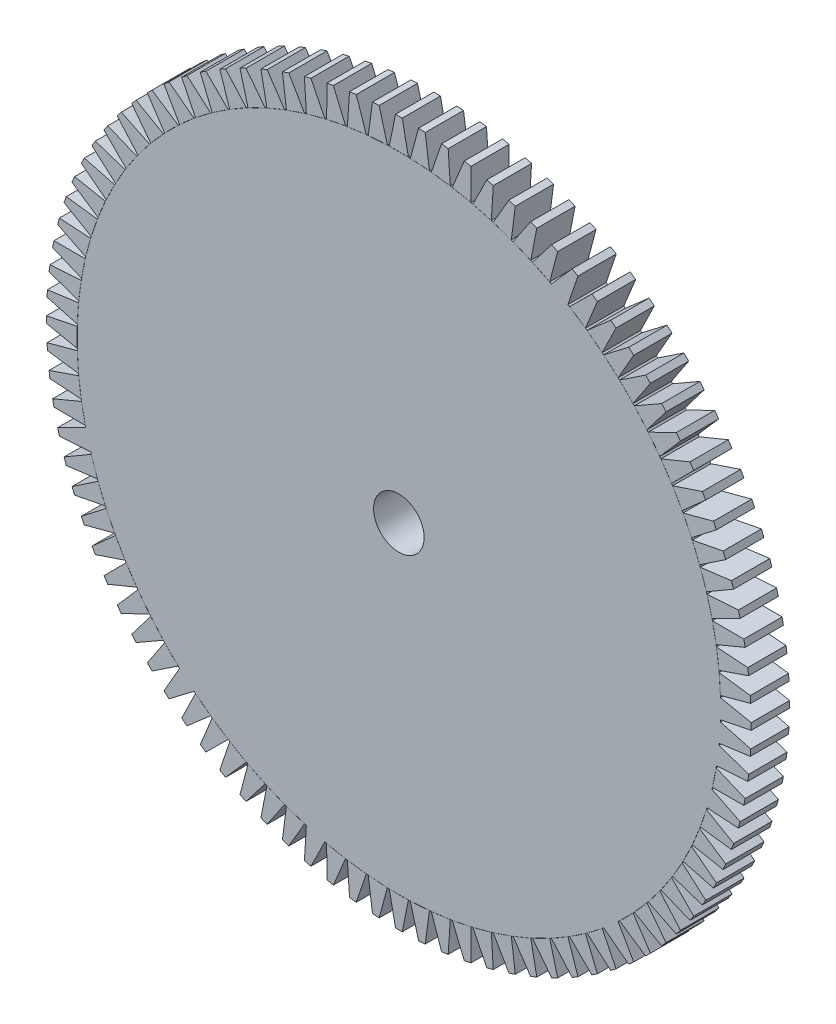
SolidWorks part; units mm, degrees
material "ABS"
ref_plane "Front Plane" through (0, 0, 0) normal (0, 0, 1) x (1, 0, 0)
ref_plane "Top Plane" through (0, 0, 0) normal (0, 1, 0) x (1, 0, 0)
ref_plane "Right Plane" through (0, 0, 0) normal (1, 0, 0) x (0, 0, -1)
sketch "Sketch1" plane through (0, 0, 0) normal (0, 0, 1) x (1, 0, 0)
  line L0 (-0.381, 12.7959) -> (0.381, 12.7959)
  line L1 (0, -15.4229) -> (0, 15.4229) construction
  line L2 (-0.1333, 14.0214) -> (0.1333, 14.0202)
  line L3 (-0.1333, 14.0214) -> (-0.381, 12.7959)
  line L4 (0.1333, 14.0202) -> (0.381, 12.7959)
  line L5 (1.05, 13.9814) -> (1.2171, 12.7436)
  line L6 (0.4567, 12.7935) -> (1.2171, 12.7436)
  line L7 (0.784, 14.0001) -> (0.4567, 12.7935)
  line L8 (0.784, 14.0001) -> (1.05, 13.9814)
  line L9 (1.9622, 13.8828) -> (2.0479, 12.6367)
  line L10 (1.2925, 12.7362) -> (2.0479, 12.6367)
  line L11 (1.698, 13.9189) -> (1.2925, 12.7362)
  line L12 (1.698, 13.9189) -> (1.9622, 13.8828)
  line L13 (2.866, 13.7248) -> (2.87, 12.4757)
  line L14 (2.1227, 12.6244) -> (2.87, 12.4757)
  line L15 (2.6047, 13.778) -> (2.1227, 12.6244)
  line L16 (2.6047, 13.778) -> (2.866, 13.7248)
  line L17 (3.7575, 13.5079) -> (3.6798, 12.2613)
  line L18 (2.9438, 12.4585) -> (3.6798, 12.2613)
  line L19 (3.5002, 13.5782) -> (2.9438, 12.4585)
  line L20 (3.5002, 13.5782) -> (3.7575, 13.5079)
  line L21 (4.6329, 13.2333) -> (4.4739, 11.9944)
  line L22 (3.7523, 12.2393) -> (4.4739, 11.9944)
  line L23 (4.3808, 13.3202) -> (3.7523, 12.2393)
  line L24 (4.3808, 13.3202) -> (4.6329, 13.2333)
  line L25 (5.4885, 12.9019) -> (5.2488, 11.6761)
  line L26 (4.5448, 11.9677) -> (5.2488, 11.6761)
  line L27 (5.2426, 13.0051) -> (4.5448, 11.9677)
  line L28 (5.2426, 13.0051) -> (5.4885, 12.9019)
  line L29 (6.3206, 12.5153) -> (6.0012, 11.3078)
  line L30 (5.3178, 11.6448) -> (6.0012, 11.3078)
  line L31 (6.0819, 12.6344) -> (5.3178, 11.6448)
  line L32 (6.0819, 12.6344) -> (6.3206, 12.5153)
  line L33 (7.1256, 12.0751) -> (6.7279, 10.8911)
  line L34 (6.068, 11.2721) -> (6.7279, 10.8911)
  line L35 (6.8952, 12.2096) -> (6.068, 11.2721)
  line L36 (6.8952, 12.2096) -> (7.1256, 12.0751)
  line L37 (7.9001, 11.5833) -> (7.4258, 10.4278)
  line L38 (6.7922, 10.8511) -> (7.4258, 10.4278)
  line L39 (7.679, 11.7325) -> (6.7922, 10.8511)
  line L40 (7.679, 11.7325) -> (7.9001, 11.5833)
  line L41 (8.6407, 11.0418) -> (8.0919, 9.9198)
  line L42 (7.4874, 10.3836) -> (8.0919, 9.9198)
  line L43 (8.4299, 11.2051) -> (7.4874, 10.3836)
  line L44 (8.4299, 11.2051) -> (8.6407, 11.0418)
  line L45 (9.3444, 10.453) -> (8.7234, 9.3693)
  line L46 (8.1505, 9.8717) -> (8.7234, 9.3693)
  line L47 (9.1447, 10.6298) -> (8.1505, 9.8717)
  line L48 (9.1447, 10.6298) -> (9.3444, 10.453)
  line L49 (10.008, 9.8195) -> (9.3175, 8.7787)
  line L50 (8.7787, 9.3175) -> (9.3175, 8.7787)
  line L51 (9.8204, 10.0089) -> (8.7787, 9.3175)
  line L52 (9.8204, 10.0089) -> (10.008, 9.8195)
  line L53 (10.6288, 9.1439) -> (9.8717, 8.1505)
  line L54 (9.3693, 8.7234) -> (9.8717, 8.1505)
  line L55 (10.4539, 9.3452) -> (9.3693, 8.7234)
  line L56 (10.4539, 9.3452) -> (10.6288, 9.1439)
  line L57 (11.2041, 8.4291) -> (10.3836, 7.4874)
  line L58 (9.9198, 8.0919) -> (10.3836, 7.4874)
  line L59 (11.0428, 8.6415) -> (9.9198, 8.0919)
  line L60 (11.0428, 8.6415) -> (11.2041, 8.4291)
  line L61 (11.7314, 7.6783) -> (10.8511, 6.7922)
  line L62 (10.4278, 7.4258) -> (10.8511, 6.7922)
  line L63 (11.5843, 7.9008) -> (10.4278, 7.4258)
  line L64 (11.5843, 7.9008) -> (11.7314, 7.6783)
  line L65 (12.2085, 6.8946) -> (11.2721, 6.068)
  line L66 (10.8911, 6.7279) -> (11.2721, 6.068)
  line L67 (12.0762, 7.1262) -> (10.8911, 6.7279)
  line L68 (12.0762, 7.1262) -> (12.2085, 6.8946)
  line L69 (12.6333, 6.0814) -> (11.6448, 5.3178)
  line L70 (11.3078, 6.0012) -> (11.6448, 5.3178)
  line L71 (12.5165, 6.3211) -> (11.3078, 6.0012)
  line L72 (12.5165, 6.3211) -> (12.6333, 6.0814)
  line L73 (13.004, 5.2421) -> (11.9677, 4.5448)
  line L74 (11.6761, 5.2488) -> (11.9677, 4.5448)
  line L75 (12.9031, 5.489) -> (11.6761, 5.2488)
  line L76 (12.9031, 5.489) -> (13.004, 5.2421)
  line L77 (13.319, 4.3804) -> (12.2393, 3.7523)
  line L78 (11.9944, 4.4739) -> (12.2393, 3.7523)
  line L79 (13.2345, 4.6333) -> (11.9944, 4.4739)
  line L80 (13.2345, 4.6333) -> (13.319, 4.3804)
  line L81 (13.577, 3.4999) -> (12.4585, 2.9438)
  line L82 (12.2613, 3.6798) -> (12.4585, 2.9438)
  line L83 (13.5092, 3.7578) -> (12.2613, 3.6798)
  line L84 (13.5092, 3.7578) -> (13.577, 3.4999)
  line L85 (13.7768, 2.6044) -> (12.6244, 2.1227)
  line L86 (12.4757, 2.87) -> (12.6244, 2.1227)
  line L87 (13.726, 2.8662) -> (12.4757, 2.87)
  line L88 (13.726, 2.8662) -> (13.7768, 2.6044)
  line L89 (13.9176, 1.6978) -> (12.7362, 1.2925)
  line L90 (12.6367, 2.0479) -> (12.7362, 1.2925)
  line L91 (13.8841, 1.9624) -> (12.6367, 2.0479)
  line L92 (13.8841, 1.9624) -> (13.9176, 1.6978)
  line L93 (13.9989, 0.7839) -> (12.7935, 0.4567)
  line L94 (12.7436, 1.2171) -> (12.7935, 0.4567)
  line L95 (13.9827, 1.0501) -> (12.7436, 1.2171)
  line L96 (13.9827, 1.0501) -> (13.9989, 0.7839)
  line L97 (14.0202, -0.1333) -> (12.7959, -0.381)
  line L98 (12.7959, 0.381) -> (12.7959, -0.381)
  line L99 (14.0214, 0.1333) -> (12.7959, 0.381)
  line L100 (14.0214, 0.1333) -> (14.0202, -0.1333)
  line L101 (13.9814, -1.05) -> (12.7436, -1.2171)
  line L102 (12.7935, -0.4567) -> (12.7436, -1.2171)
  line L103 (14.0001, -0.784) -> (12.7935, -0.4567)
  line L104 (14.0001, -0.784) -> (13.9814, -1.05)
  line L105 (13.8828, -1.9622) -> (12.6367, -2.0479)
  line L106 (12.7362, -1.2925) -> (12.6367, -2.0479)
  line L107 (13.9189, -1.698) -> (12.7362, -1.2925)
  line L108 (13.9189, -1.698) -> (13.8828, -1.9622)
  line L109 (13.7248, -2.866) -> (12.4757, -2.87)
  line L110 (12.6244, -2.1227) -> (12.4757, -2.87)
  line L111 (13.778, -2.6047) -> (12.6244, -2.1227)
  line L112 (13.778, -2.6047) -> (13.7248, -2.866)
  line L113 (13.5079, -3.7575) -> (12.2613, -3.6798)
  line L114 (12.4585, -2.9438) -> (12.2613, -3.6798)
  line L115 (13.5782, -3.5002) -> (12.4585, -2.9438)
  line L116 (13.5782, -3.5002) -> (13.5079, -3.7575)
  line L117 (13.2333, -4.6329) -> (11.9944, -4.4739)
  line L118 (12.2393, -3.7523) -> (11.9944, -4.4739)
  line L119 (13.3202, -4.3808) -> (12.2393, -3.7523)
  line L120 (13.3202, -4.3808) -> (13.2333, -4.6329)
  line L121 (12.9019, -5.4885) -> (11.6761, -5.2488)
  line L122 (11.9677, -4.5448) -> (11.6761, -5.2488)
  line L123 (13.0051, -5.2426) -> (11.9677, -4.5448)
  line L124 (13.0051, -5.2426) -> (12.9019, -5.4885)
  line L125 (12.5153, -6.3206) -> (11.3078, -6.0012)
  line L126 (11.6448, -5.3178) -> (11.3078, -6.0012)
  line L127 (12.6344, -6.0819) -> (11.6448, -5.3178)
  line L128 (12.6344, -6.0819) -> (12.5153, -6.3206)
  line L129 (12.0751, -7.1256) -> (10.8911, -6.7279)
  line L130 (11.2721, -6.068) -> (10.8911, -6.7279)
  line L131 (12.2096, -6.8952) -> (11.2721, -6.068)
  line L132 (12.2096, -6.8952) -> (12.0751, -7.1256)
  line L133 (11.5833, -7.9001) -> (10.4278, -7.4258)
  line L134 (10.8511, -6.7922) -> (10.4278, -7.4258)
  line L135 (11.7325, -7.679) -> (10.8511, -6.7922)
  line L136 (11.7325, -7.679) -> (11.5833, -7.9001)
  line L137 (11.0418, -8.6407) -> (9.9198, -8.0919)
  line L138 (10.3836, -7.4874) -> (9.9198, -8.0919)
  line L139 (11.2051, -8.4299) -> (10.3836, -7.4874)
  line L140 (11.2051, -8.4299) -> (11.0418, -8.6407)
  line L141 (10.453, -9.3444) -> (9.3693, -8.7234)
  line L142 (9.8717, -8.1505) -> (9.3693, -8.7234)
  line L143 (10.6298, -9.1447) -> (9.8717, -8.1505)
  line L144 (10.6298, -9.1447) -> (10.453, -9.3444)
  line L145 (9.8195, -10.008) -> (8.7787, -9.3175)
  line L146 (9.3175, -8.7787) -> (8.7787, -9.3175)
  line L147 (10.0089, -9.8204) -> (9.3175, -8.7787)
  line L148 (10.0089, -9.8204) -> (9.8195, -10.008)
  line L149 (9.1439, -10.6288) -> (8.1505, -9.8717)
  line L150 (8.7234, -9.3693) -> (8.1505, -9.8717)
  line L151 (9.3452, -10.4539) -> (8.7234, -9.3693)
  line L152 (9.3452, -10.4539) -> (9.1439, -10.6288)
  line L153 (8.4291, -11.2041) -> (7.4874, -10.3836)
  line L154 (8.0919, -9.9198) -> (7.4874, -10.3836)
  line L155 (8.6415, -11.0428) -> (8.0919, -9.9198)
  line L156 (8.6415, -11.0428) -> (8.4291, -11.2041)
  line L157 (7.6783, -11.7314) -> (6.7922, -10.8511)
  line L158 (7.4258, -10.4278) -> (6.7922, -10.8511)
  line L159 (7.9008, -11.5843) -> (7.4258, -10.4278)
  line L160 (7.9008, -11.5843) -> (7.6783, -11.7314)
  line L161 (6.8946, -12.2085) -> (6.068, -11.2721)
  line L162 (6.7279, -10.8911) -> (6.068, -11.2721)
  line L163 (7.1262, -12.0762) -> (6.7279, -10.8911)
  line L164 (7.1262, -12.0762) -> (6.8946, -12.2085)
  line L165 (6.0814, -12.6333) -> (5.3178, -11.6448)
  line L166 (6.0012, -11.3078) -> (5.3178, -11.6448)
  line L167 (6.3211, -12.5165) -> (6.0012, -11.3078)
  line L168 (6.3211, -12.5165) -> (6.0814, -12.6333)
  line L169 (5.2421, -13.004) -> (4.5448, -11.9677)
  line L170 (5.2488, -11.6761) -> (4.5448, -11.9677)
  line L171 (5.489, -12.9031) -> (5.2488, -11.6761)
  line L172 (5.489, -12.9031) -> (5.2421, -13.004)
  line L173 (4.3804, -13.319) -> (3.7523, -12.2393)
  line L174 (4.4739, -11.9944) -> (3.7523, -12.2393)
  line L175 (4.6333, -13.2345) -> (4.4739, -11.9944)
  line L176 (4.6333, -13.2345) -> (4.3804, -13.319)
  line L177 (3.4999, -13.577) -> (2.9438, -12.4585)
  line L178 (3.6798, -12.2613) -> (2.9438, -12.4585)
  line L179 (3.7578, -13.5092) -> (3.6798, -12.2613)
  line L180 (3.7578, -13.5092) -> (3.4999, -13.577)
  line L181 (2.6044, -13.7768) -> (2.1227, -12.6244)
  line L182 (2.87, -12.4757) -> (2.1227, -12.6244)
  line L183 (2.8662, -13.726) -> (2.87, -12.4757)
  line L184 (2.8662, -13.726) -> (2.6044, -13.7768)
  line L185 (1.6978, -13.9176) -> (1.2925, -12.7362)
  line L186 (2.0479, -12.6367) -> (1.2925, -12.7362)
  line L187 (1.9624, -13.8841) -> (2.0479, -12.6367)
  line L188 (1.9624, -13.8841) -> (1.6978, -13.9176)
  line L189 (0.7839, -13.9989) -> (0.4567, -12.7935)
  line L190 (1.2171, -12.7436) -> (0.4567, -12.7935)
  line L191 (1.0501, -13.9827) -> (1.2171, -12.7436)
  line L192 (1.0501, -13.9827) -> (0.7839, -13.9989)
  line L193 (-0.1333, -14.0202) -> (-0.381, -12.7959)
  line L194 (0.381, -12.7959) -> (-0.381, -12.7959)
  line L195 (0.1333, -14.0214) -> (0.381, -12.7959)
  line L196 (0.1333, -14.0214) -> (-0.1333, -14.0202)
  line L197 (-1.05, -13.9814) -> (-1.2171, -12.7436)
  line L198 (-0.4567, -12.7935) -> (-1.2171, -12.7436)
  line L199 (-0.784, -14.0001) -> (-0.4567, -12.7935)
  line L200 (-0.784, -14.0001) -> (-1.05, -13.9814)
  line L201 (-1.9622, -13.8828) -> (-2.0479, -12.6367)
  line L202 (-1.2925, -12.7362) -> (-2.0479, -12.6367)
  line L203 (-1.698, -13.9189) -> (-1.2925, -12.7362)
  line L204 (-1.698, -13.9189) -> (-1.9622, -13.8828)
  line L205 (-2.866, -13.7248) -> (-2.87, -12.4757)
  line L206 (-2.1227, -12.6244) -> (-2.87, -12.4757)
  line L207 (-2.6047, -13.778) -> (-2.1227, -12.6244)
  line L208 (-2.6047, -13.778) -> (-2.866, -13.7248)
  line L209 (-3.7575, -13.5079) -> (-3.6798, -12.2613)
  line L210 (-2.9438, -12.4585) -> (-3.6798, -12.2613)
  line L211 (-3.5002, -13.5782) -> (-2.9438, -12.4585)
  line L212 (-3.5002, -13.5782) -> (-3.7575, -13.5079)
  line L213 (-4.6329, -13.2333) -> (-4.4739, -11.9944)
  line L214 (-3.7523, -12.2393) -> (-4.4739, -11.9944)
  line L215 (-4.3808, -13.3202) -> (-3.7523, -12.2393)
  line L216 (-4.3808, -13.3202) -> (-4.6329, -13.2333)
  line L217 (-5.4885, -12.9019) -> (-5.2488, -11.6761)
  line L218 (-4.5448, -11.9677) -> (-5.2488, -11.6761)
  line L219 (-5.2426, -13.0051) -> (-4.5448, -11.9677)
  line L220 (-5.2426, -13.0051) -> (-5.4885, -12.9019)
  line L221 (-6.3206, -12.5153) -> (-6.0012, -11.3078)
  line L222 (-5.3178, -11.6448) -> (-6.0012, -11.3078)
  line L223 (-6.0819, -12.6344) -> (-5.3178, -11.6448)
  line L224 (-6.0819, -12.6344) -> (-6.3206, -12.5153)
  line L225 (-7.1256, -12.0751) -> (-6.7279, -10.8911)
  line L226 (-6.068, -11.2721) -> (-6.7279, -10.8911)
  line L227 (-6.8952, -12.2096) -> (-6.068, -11.2721)
  line L228 (-6.8952, -12.2096) -> (-7.1256, -12.0751)
  line L229 (-7.9001, -11.5833) -> (-7.4258, -10.4278)
  line L230 (-6.7922, -10.8511) -> (-7.4258, -10.4278)
  line L231 (-7.679, -11.7325) -> (-6.7922, -10.8511)
  line L232 (-7.679, -11.7325) -> (-7.9001, -11.5833)
  line L233 (-8.6407, -11.0418) -> (-8.0919, -9.9198)
  line L234 (-7.4874, -10.3836) -> (-8.0919, -9.9198)
  line L235 (-8.4299, -11.2051) -> (-7.4874, -10.3836)
  line L236 (-8.4299, -11.2051) -> (-8.6407, -11.0418)
  line L237 (-9.3444, -10.453) -> (-8.7234, -9.3693)
  line L238 (-8.1505, -9.8717) -> (-8.7234, -9.3693)
  line L239 (-9.1447, -10.6298) -> (-8.1505, -9.8717)
  line L240 (-9.1447, -10.6298) -> (-9.3444, -10.453)
  line L241 (-10.008, -9.8195) -> (-9.3175, -8.7787)
  line L242 (-8.7787, -9.3175) -> (-9.3175, -8.7787)
  line L243 (-9.8204, -10.0089) -> (-8.7787, -9.3175)
  line L244 (-9.8204, -10.0089) -> (-10.008, -9.8195)
  line L245 (-10.6288, -9.1439) -> (-9.8717, -8.1505)
  line L246 (-9.3693, -8.7234) -> (-9.8717, -8.1505)
  line L247 (-10.4539, -9.3452) -> (-9.3693, -8.7234)
  line L248 (-10.4539, -9.3452) -> (-10.6288, -9.1439)
  line L249 (-11.2041, -8.4291) -> (-10.3836, -7.4874)
  line L250 (-9.9198, -8.0919) -> (-10.3836, -7.4874)
  line L251 (-11.0428, -8.6415) -> (-9.9198, -8.0919)
  line L252 (-11.0428, -8.6415) -> (-11.2041, -8.4291)
  line L253 (-11.7314, -7.6783) -> (-10.8511, -6.7922)
  line L254 (-10.4278, -7.4258) -> (-10.8511, -6.7922)
  line L255 (-11.5843, -7.9008) -> (-10.4278, -7.4258)
  line L256 (-11.5843, -7.9008) -> (-11.7314, -7.6783)
  line L257 (-12.2085, -6.8946) -> (-11.2721, -6.068)
  line L258 (-10.8911, -6.7279) -> (-11.2721, -6.068)
  line L259 (-12.0762, -7.1262) -> (-10.8911, -6.7279)
  line L260 (-12.0762, -7.1262) -> (-12.2085, -6.8946)
  line L261 (-12.6333, -6.0814) -> (-11.6448, -5.3178)
  line L262 (-11.3078, -6.0012) -> (-11.6448, -5.3178)
  line L263 (-12.5165, -6.3211) -> (-11.3078, -6.0012)
  line L264 (-12.5165, -6.3211) -> (-12.6333, -6.0814)
  line L265 (-13.004, -5.2421) -> (-11.9677, -4.5448)
  line L266 (-11.6761, -5.2488) -> (-11.9677, -4.5448)
  line L267 (-12.9031, -5.489) -> (-11.6761, -5.2488)
  line L268 (-12.9031, -5.489) -> (-13.004, -5.2421)
  line L269 (-13.319, -4.3804) -> (-12.2393, -3.7523)
  line L270 (-11.9944, -4.4739) -> (-12.2393, -3.7523)
  line L271 (-13.2345, -4.6333) -> (-11.9944, -4.4739)
  line L272 (-13.2345, -4.6333) -> (-13.319, -4.3804)
  line L273 (-13.577, -3.4999) -> (-12.4585, -2.9438)
  line L274 (-12.2613, -3.6798) -> (-12.4585, -2.9438)
  line L275 (-13.5092, -3.7578) -> (-12.2613, -3.6798)
  line L276 (-13.5092, -3.7578) -> (-13.577, -3.4999)
  line L277 (-13.7768, -2.6044) -> (-12.6244, -2.1227)
  line L278 (-12.4757, -2.87) -> (-12.6244, -2.1227)
  line L279 (-13.726, -2.8662) -> (-12.4757, -2.87)
  line L280 (-13.726, -2.8662) -> (-13.7768, -2.6044)
  line L281 (-13.9176, -1.6978) -> (-12.7362, -1.2925)
  line L282 (-12.6367, -2.0479) -> (-12.7362, -1.2925)
  line L283 (-13.8841, -1.9624) -> (-12.6367, -2.0479)
  line L284 (-13.8841, -1.9624) -> (-13.9176, -1.6978)
  line L285 (-13.9989, -0.7839) -> (-12.7935, -0.4567)
  line L286 (-12.7436, -1.2171) -> (-12.7935, -0.4567)
  line L287 (-13.9827, -1.0501) -> (-12.7436, -1.2171)
  line L288 (-13.9827, -1.0501) -> (-13.9989, -0.7839)
  line L289 (-14.0202, 0.1333) -> (-12.7959, 0.381)
  line L290 (-12.7959, -0.381) -> (-12.7959, 0.381)
  line L291 (-14.0214, -0.1333) -> (-12.7959, -0.381)
  line L292 (-14.0214, -0.1333) -> (-14.0202, 0.1333)
  line L293 (-13.9814, 1.05) -> (-12.7436, 1.2171)
  line L294 (-12.7935, 0.4567) -> (-12.7436, 1.2171)
  line L295 (-14.0001, 0.784) -> (-12.7935, 0.4567)
  line L296 (-14.0001, 0.784) -> (-13.9814, 1.05)
  line L297 (-13.8828, 1.9622) -> (-12.6367, 2.0479)
  line L298 (-12.7362, 1.2925) -> (-12.6367, 2.0479)
  line L299 (-13.9189, 1.698) -> (-12.7362, 1.2925)
  line L300 (-13.9189, 1.698) -> (-13.8828, 1.9622)
  line L301 (-13.7248, 2.866) -> (-12.4757, 2.87)
  line L302 (-12.6244, 2.1227) -> (-12.4757, 2.87)
  line L303 (-13.778, 2.6047) -> (-12.6244, 2.1227)
  line L304 (-13.778, 2.6047) -> (-13.7248, 2.866)
  line L305 (-13.5079, 3.7575) -> (-12.2613, 3.6798)
  line L306 (-12.4585, 2.9438) -> (-12.2613, 3.6798)
  line L307 (-13.5782, 3.5002) -> (-12.4585, 2.9438)
  line L308 (-13.5782, 3.5002) -> (-13.5079, 3.7575)
  line L309 (-13.2333, 4.6329) -> (-11.9944, 4.4739)
  line L310 (-12.2393, 3.7523) -> (-11.9944, 4.4739)
  line L311 (-13.3202, 4.3808) -> (-12.2393, 3.7523)
  line L312 (-13.3202, 4.3808) -> (-13.2333, 4.6329)
  line L313 (-12.9019, 5.4885) -> (-11.6761, 5.2488)
  line L314 (-11.9677, 4.5448) -> (-11.6761, 5.2488)
  line L315 (-13.0051, 5.2426) -> (-11.9677, 4.5448)
  line L316 (-13.0051, 5.2426) -> (-12.9019, 5.4885)
  line L317 (-12.5153, 6.3206) -> (-11.3078, 6.0012)
  line L318 (-11.6448, 5.3178) -> (-11.3078, 6.0012)
  line L319 (-12.6344, 6.0819) -> (-11.6448, 5.3178)
  line L320 (-12.6344, 6.0819) -> (-12.5153, 6.3206)
  line L321 (-12.0751, 7.1256) -> (-10.8911, 6.7279)
  line L322 (-11.2721, 6.068) -> (-10.8911, 6.7279)
  line L323 (-12.2096, 6.8952) -> (-11.2721, 6.068)
  line L324 (-12.2096, 6.8952) -> (-12.0751, 7.1256)
  line L325 (-11.5833, 7.9001) -> (-10.4278, 7.4258)
  line L326 (-10.8511, 6.7922) -> (-10.4278, 7.4258)
  line L327 (-11.7325, 7.679) -> (-10.8511, 6.7922)
  line L328 (-11.7325, 7.679) -> (-11.5833, 7.9001)
  line L329 (-11.0418, 8.6407) -> (-9.9198, 8.0919)
  line L330 (-10.3836, 7.4874) -> (-9.9198, 8.0919)
  line L331 (-11.2051, 8.4299) -> (-10.3836, 7.4874)
  line L332 (-11.2051, 8.4299) -> (-11.0418, 8.6407)
  line L333 (-10.453, 9.3444) -> (-9.3693, 8.7234)
  line L334 (-9.8717, 8.1505) -> (-9.3693, 8.7234)
  line L335 (-10.6298, 9.1447) -> (-9.8717, 8.1505)
  line L336 (-10.6298, 9.1447) -> (-10.453, 9.3444)
  line L337 (-9.8195, 10.008) -> (-8.7787, 9.3175)
  line L338 (-9.3175, 8.7787) -> (-8.7787, 9.3175)
  line L339 (-10.0089, 9.8204) -> (-9.3175, 8.7787)
  line L340 (-10.0089, 9.8204) -> (-9.8195, 10.008)
  line L341 (-9.1439, 10.6288) -> (-8.1505, 9.8717)
  line L342 (-8.7234, 9.3693) -> (-8.1505, 9.8717)
  line L343 (-9.3452, 10.4539) -> (-8.7234, 9.3693)
  line L344 (-9.3452, 10.4539) -> (-9.1439, 10.6288)
  line L345 (-8.4291, 11.2041) -> (-7.4874, 10.3836)
  line L346 (-8.0919, 9.9198) -> (-7.4874, 10.3836)
  line L347 (-8.6415, 11.0428) -> (-8.0919, 9.9198)
  line L348 (-8.6415, 11.0428) -> (-8.4291, 11.2041)
  line L349 (-7.6783, 11.7314) -> (-6.7922, 10.8511)
  line L350 (-7.4258, 10.4278) -> (-6.7922, 10.8511)
  line L351 (-7.9008, 11.5843) -> (-7.4258, 10.4278)
  line L352 (-7.9008, 11.5843) -> (-7.6783, 11.7314)
  line L353 (-6.8946, 12.2085) -> (-6.068, 11.2721)
  line L354 (-6.7279, 10.8911) -> (-6.068, 11.2721)
  line L355 (-7.1262, 12.0762) -> (-6.7279, 10.8911)
  line L356 (-7.1262, 12.0762) -> (-6.8946, 12.2085)
  line L357 (-6.0814, 12.6333) -> (-5.3178, 11.6448)
  line L358 (-6.0012, 11.3078) -> (-5.3178, 11.6448)
  line L359 (-6.3211, 12.5165) -> (-6.0012, 11.3078)
  line L360 (-6.3211, 12.5165) -> (-6.0814, 12.6333)
  line L361 (-5.2421, 13.004) -> (-4.5448, 11.9677)
  line L362 (-5.2488, 11.6761) -> (-4.5448, 11.9677)
  line L363 (-5.489, 12.9031) -> (-5.2488, 11.6761)
  line L364 (-5.489, 12.9031) -> (-5.2421, 13.004)
  line L365 (-4.3804, 13.319) -> (-3.7523, 12.2393)
  line L366 (-4.4739, 11.9944) -> (-3.7523, 12.2393)
  line L367 (-4.6333, 13.2345) -> (-4.4739, 11.9944)
  line L368 (-4.6333, 13.2345) -> (-4.3804, 13.319)
  line L369 (-3.4999, 13.577) -> (-2.9438, 12.4585)
  line L370 (-3.6798, 12.2613) -> (-2.9438, 12.4585)
  line L371 (-3.7578, 13.5092) -> (-3.6798, 12.2613)
  line L372 (-3.7578, 13.5092) -> (-3.4999, 13.577)
  line L373 (-2.6044, 13.7768) -> (-2.1227, 12.6244)
  line L374 (-2.87, 12.4757) -> (-2.1227, 12.6244)
  line L375 (-2.8662, 13.726) -> (-2.87, 12.4757)
  line L376 (-2.8662, 13.726) -> (-2.6044, 13.7768)
  line L377 (-1.6978, 13.9176) -> (-1.2925, 12.7362)
  line L378 (-2.0479, 12.6367) -> (-1.2925, 12.7362)
  line L379 (-1.9624, 13.8841) -> (-2.0479, 12.6367)
  line L380 (-1.9624, 13.8841) -> (-1.6978, 13.9176)
  line L381 (-0.7839, 13.9989) -> (-0.4567, 12.7935)
  line L382 (-1.2171, 12.7436) -> (-0.4567, 12.7935)
  line L383 (-1.0501, 13.9827) -> (-1.2171, 12.7436)
  line L384 (-1.0501, 13.9827) -> (-0.7839, 13.9989)
  circle A0 centre (0, 0) radius 14.0208 construction
  circle A1 centre (0, 0) radius 12.8016
  point P8 (0, 12.7959)
  point P13 (0, 14.0208)
  point P396 (0, 0)
  dimension "D1" = 28.0416
  dimension "D3" = 0.762
  dimension "D4" = 0.2667
  dimension "D2" = 1.2192
  dimension "D5" = 96
extrude "Boss-Extrude1" add sketch "Sketch1" along normal blind 1.524 contours L98 A1 L94 L90 L86 L82 L78 L74 L70 L66 L62 L58 L54 L50 L46 L42 L38 L34 L30 L26 L22 L18 L14 L10 L6 L0 L382 | A1 L353 L356 L355 | A1 L357 L360 L359 | A1 L349 L352 L351 | A1 L345 L348 L347 | A1 L341 L344 L343 | A1 L337 L340 L339 | A1 L333 L336 L335 | A1 L329 L332 L331 | A1 L325 L328 L327 | A1 L321 L324 L323 | A1 L317 L320 L319 | A1 L313 L316 L315 | A1 L309 L312 L311 | A1 L305 L308 L307 | A1 L301 L304 L303 | A1 L297 L300 L299 | A1 L293 L296 L295 | A1 L289 L292 L291 | A1 L285 L288 L287 | A1 L281 L284 L283 | A1 L277 L280 L279 | A1 L269 L272 L271 | A1 L265 L268 L267 | A1 L261 L264 L263 | A1 L257 L260 L259 | A1 L253 L256 L255 | A1 L249 L252 L251 | A1 L245 L248 L247 | A1 L241 L244 L243 | A1 L233 L236 L235 | A1 L229 L232 L231 | A1 L225 L228 L227 | A1 L221 L224 L223 | A1 L361 L364 L363 | A1 L365 L368 L367 | A1 L369 L372 L371 | A1 L373 L376 L375 | A1 L377 L380 L379 | A1 L381 L384 L383 | A1 L4 L2 L3 | A1 L5 L8 L7 | A1 L9 L12 L11 | A1 L13 L16 L15 | A1 L17 L20 L19 | A1 L21 L24 L23 | A1 L25 L28 L27 | A1 L109 L112 L111 | A1 L93 L96 L95 | A1 L89 L92 L91 | A1 L85 L88 L87 | A1 L81 L84 L83 | A1 L77 L80 L79 | A1 L73 L76 L75 | A1 L69 L72 L71 | A1 L65 L68 L67 | A1 L61 L64 L63 | A1 L57 L60 L59 | A1 L53 L56 L55 | A1 L49 L52 L51 | A1 L45 L48 L47 | A1 L41 L44 L43 | A1 L37 L40 L39 | A1 L29 L32 L31 | A1 L117 L120 L119 | A1 L121 L124 L123 | A1 L125 L128 L127 | A1 L129 L132 L131 | A1 L133 L136 L135 | A1 L137 L140 L139 | A1 L141 L144 L143 | A1 L145 L148 L147 | A1 L153 L156 L155 | A1 L157 L160 L159 | A1 L161 L164 L163 | A1 L165 L168 L167 | A1 L169 L172 L171 | A1 L173 L176 L175 | A1 L177 L180 L179 | A1 L181 L184 L183 | A1 L185 L188 L187 | A1 L189 L192 L191 | A1 L193 L196 L195 | A1 L197 L200 L199 | A1 L201 L204 L203 | A1 L205 L208 L207 | A1 L213 L216 L215 | A1 L217 L220 L219 | L275 L274 L273 L276 | L239 L238 L237 L240 | L115 L114 L113 L116 | L105 L106 L107 L108 | L101 L102 L103 L104 | L97 L98 L99 L100 | L33 L34 L35 L36 | L151 L150 L149 L152 | L209 L210 L211 L212 region at (-0.0001, 13.3124, 0) region at (0, 0, 0) region at (-0.8707, 13.2839, 0) region at (0.8706, 13.2839, 0) region at (-1.7377, 13.1985, 0) region at (1.7376, 13.1985, 0) region at (-2.5972, 13.0566, 0) region at (2.5971, 13.0566, 0) region at (-3.4456, 12.8588, 0) region at (3.4454, 12.8588, 0) region at (-4.2792, 12.6059, 0) region at (4.2791, 12.606, 0) region at (-5.0945, 12.299, 0) region at (5.0944, 12.2991, 0) region at (-5.888, 11.9395, 0) region at (5.8879, 11.9396, 0) region at (-6.6563, 11.5289, 0) region at (-7.396, 11.0688, 0) region at (7.3959, 11.0689, 0) region at (-8.1041, 10.5614, 0) region at (8.104, 10.5615, 0) region at (-8.7775, 10.0088, 0) region at (8.7774, 10.0089, 0) region at (-9.4134, 9.4133, 0) region at (9.4133, 9.4134, 0) region at (-10.0089, 8.7774, 0) region at (10.0088, 8.7775, 0) region at (-10.5615, 8.104, 0) region at (10.5614, 8.1041, 0) region at (-11.0689, 7.3959, 0) region at (11.0688, 7.396, 0) region at (-11.5289, 6.6562, 0) region at (11.5289, 6.6563, 0) region at (-11.9396, 5.8879, 0) region at (11.9395, 5.888, 0) region at (-12.2991, 5.0944, 0) region at (12.299, 5.0945, 0) region at (-12.606, 4.2791, 0) region at (12.6059, 4.2792, 0) region at (-12.8588, 3.4454, 0) region at (12.8588, 3.4456, 0) region at (-13.0566, 2.5971, 0) region at (13.0566, 2.5972, 0) region at (-13.1985, 1.7376, 0) region at (13.1985, 1.7377, 0) region at (-13.2839, 0.8706, 0) region at (13.2839, 0.8707, 0) region at (-13.3124, -0.0001, 0) region at (-13.2839, -0.8707, 0) region at (-13.1985, -1.7377, 0) region at (-13.0566, -2.5972, 0) region at (13.0566, -2.5971, 0) region at (-12.6059, -4.2792, 0) region at (12.606, -4.2791, 0) region at (-12.299, -5.0945, 0) region at (12.2991, -5.0944, 0) region at (-11.9395, -5.888, 0) region at (11.9396, -5.8879, 0) region at (-11.5289, -6.6563, 0) region at (11.5289, -6.6562, 0)
sketch "Sketch2" plane through (0, 0, 1.524) normal (0, 0, 1) x (1, 0, 0)
  circle A0 centre (0, 0) radius 1.0058
  dimension "D1" = 2.0117
extrude "Cut-Extrude1" cut sketch "Sketch2" against normal blind 1.524
